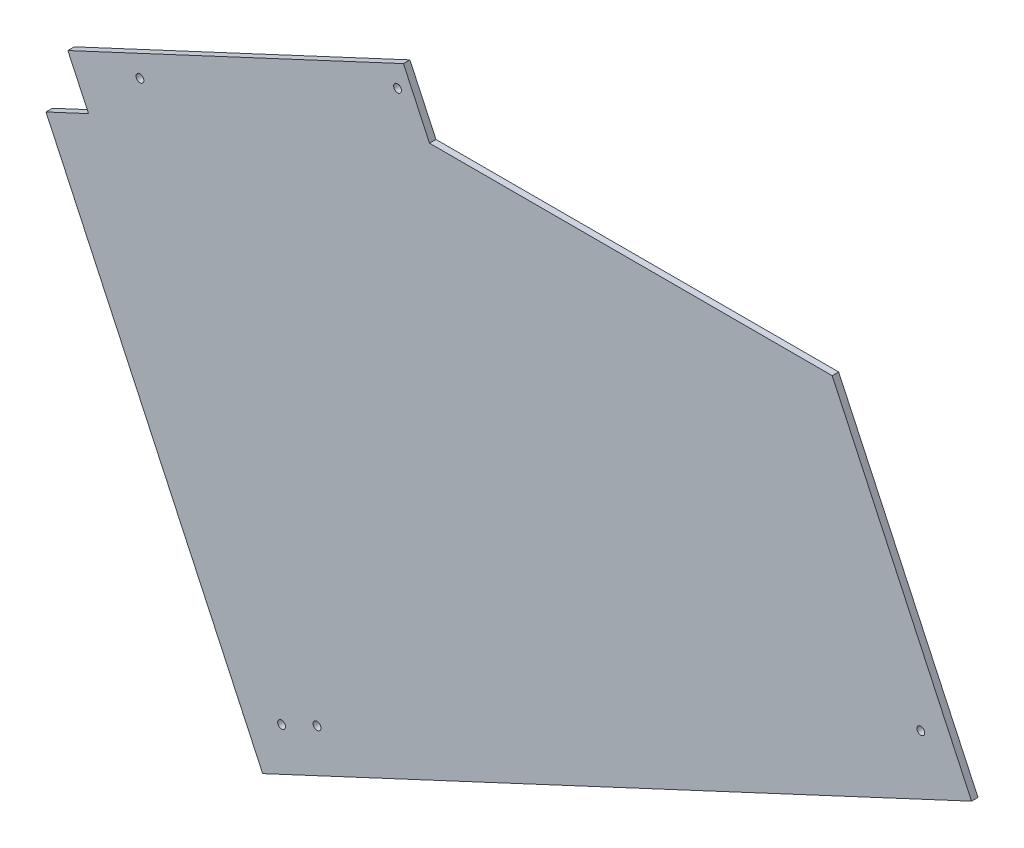
SolidWorks part; units mm, degrees
ref_plane "Front Plane" through (0, 0, 0) normal (0, 0, 1) x (1, 0, 0)
ref_plane "Top Plane" through (0, 0, 0) normal (0, 1, 0) x (1, 0, 0)
ref_plane "Right Plane" through (0, 0, 0) normal (1, 0, 0) x (0, 0, -1)
sketch "Sketch1" plane through (0, 0, 0) normal (0, 0, 1) x (1, 0, 0)
  line L0 (327.4362, 0.0035) -> (121.4984, 0.0035)
  line L1 (121.4984, 0.0035) -> (108.169, 28.5884)
  line L2 (108.169, 28.5884) -> (-63.4467, -51.4373)
  line L3 (-63.4467, -51.4373) -> (57.9293, -311.7289) construction
  line L4 (57.9293, -311.7289) -> (398.701, -152.8244)
  line L5 (271.5352, 119.8836) -> (277.3251, 107.4672) construction
  line L6 (190.5834, 136.311) -> (-12.0446, 41.824) construction
  line L7 (-63.4467, -51.4373) -> (255.5737, 97.3243) construction
  line L8 (398.701, -152.8244) -> (327.4362, 0.0035)
  line L9 (57.9293, -311.7289) -> (36.1779, -321.8717)
  line L10 (36.1779, -321.8717) -> (-74.6326, -84.2378)
  line L11 (50.7481, 0) -> (323.7481, 0) construction
  line L12 (-74.6326, -84.2378) -> (-52.8812, -74.095)
  line L13 (-90.9879, -49.1637) -> (-85.1981, -61.5801) construction
  line L14 (-52.8812, -74.095) -> (-63.4467, -51.4373)
  circle A0 centre (162.7613, -40.6644) radius 32.5 construction
  circle A1 centre (336.0773, -108.8767) radius 32.5 construction
  circle A2 centre (90.1802, -40.6644) radius 32.5 construction
  circle A3 centre (232.5481, -40.6644) radius 32.5 construction
  circle A4 centre (207.2768, 100.5118) radius 39.5 construction
  arc A5 (-3.3339, 41.4724) -> (-17.3744, 34.9252) centre (-8.0297, 33.2141) ccw construction
  circle A6 centre (304.5287, -40.6644) radius 32.5 construction
  circle A7 centre (254.9584, -108.8767) radius 32.5 construction
  circle A8 centre (179.3206, -108.8767) radius 32.5 construction
  circle A9 centre (101.4264, -108.8767) radius 32.5 construction
  circle A10 centre (270.383, -163.8108) radius 32.5 construction
  circle A11 centre (372.7594, -134.5783) radius 2
  dimension "D2" = 65
  dimension "D3" = 65
  dimension "D5" = 4
  dimension "D1" = 350
  dimension "D4" = 25
  dimension "24.5/2" = 15.8
  dimension "D6" = 27.5
extrude "Boss-Extrude1" add sketch "Sketch1" along normal up to surface (3.3 mm away)
sketch "Sketch2" plane through (0, 0, 3.3) normal (0, 0, 1) x (1, 0, 0)
  circle A0 centre (105.1447, 16.1444) radius 2
  circle A1 centre (-26.5934, -45.2861) radius 2
  circle A2 centre (-26.5934, -45.2861) radius 2 construction
  circle A3 centre (105.1447, 16.1444) radius 2 construction
extrude "Cut-Extrude1" cut sketch "Sketch2" against normal through all
sketch "Sketch3" plane through (0, 0, 3.3) normal (0, 0, 1) x (1, 0, 0)
  circle A0 centre (45.8517, -295.2932) radius 2
  circle A1 centre (63.9779, -286.8408) radius 2
  circle A2 centre (63.9779, -286.8408) radius 2 construction
  circle A3 centre (45.8517, -295.2932) radius 2 construction
  point P6 (0, 0)
  point P9 (0, 0)
  dimension "D1" = 4
  dimension "D2" = 4
extrude "Cut-Extrude2" cut sketch "Sketch3" against normal blind 4
